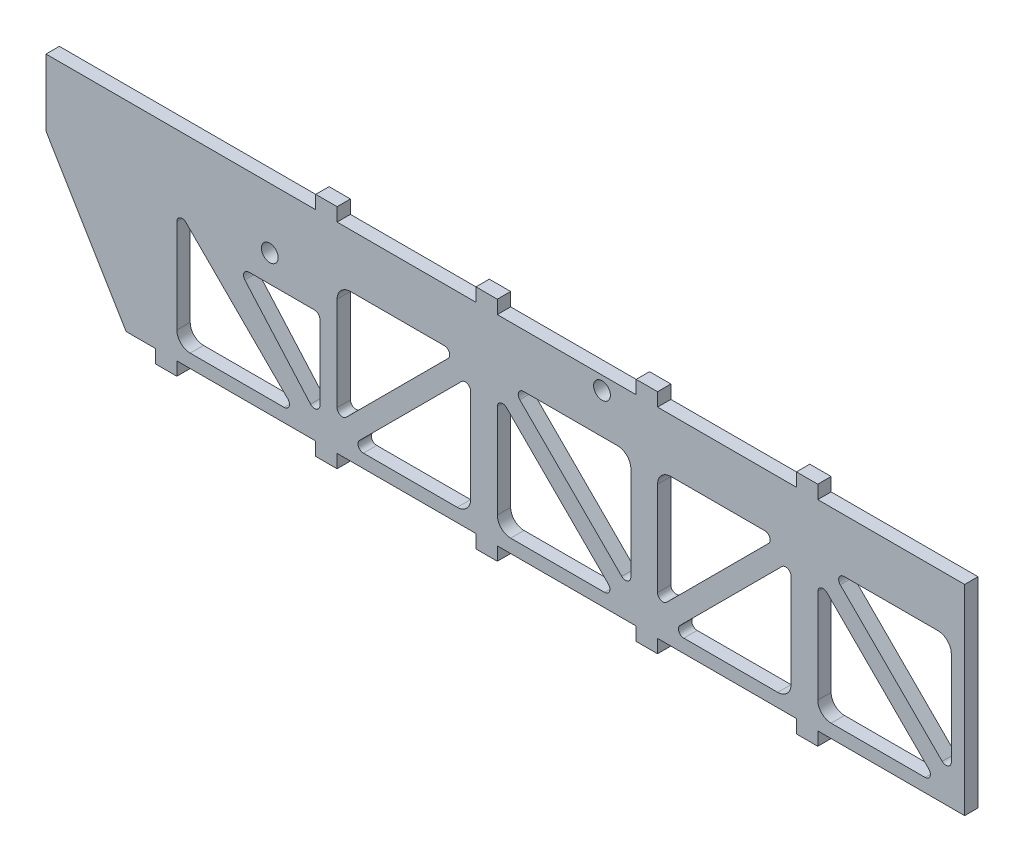
SolidWorks part; units mm, degrees
material "Pine"
ref_plane "Front Plane" through (0, 0, 0) normal (0, 0, 1) x (1, 0, 0)
ref_plane "Top Plane" through (0, 0, 0) normal (0, 1, 0) x (1, 0, 0)
ref_plane "Right Plane" through (0, 0, 0) normal (1, 0, 0) x (0, 0, -1)
sketch "Model" plane through (0, 0, 0) normal (0, 0, 1) x (1, 0, 0)
  line L0 (-306.6281, 15.625) -> (-306.6281, 51.1493)
  line L1 (-309.1681, 53.6893) -> (-340.406, 53.6893)
  line L2 (-342.3135, 49.472) -> (-311.0755, 13.9477)
  line L8 (-171.2321, 6.35) -> (-215.9, 6.35)
  line L9 (-222.25, 57.3679) -> (-222.25, 12.7)
  line L10 (-217.9139, 59.1639) -> (-169.4361, 10.6861)
  line L11 (-234.95, 57.3679) -> (-234.95, 12.7)
  line L12 (-241.3, 6.35) -> (-285.9679, 6.35)
  line L13 (-239.2861, 59.1639) -> (-287.7639, 10.6861)
  line L14 (-294.1139, 17.0361) -> (-245.6361, 65.5139)
  line L15 (-298.45, 63.5) -> (-298.45, 18.8321)
  line L16 (-247.4321, 69.85) -> (-292.1, 69.85)
  line L17 (-323.6321, 6.35) -> (-368.3, 6.35)
  line L18 (-374.65, 57.3679) -> (-374.65, 12.7)
  line L19 (-370.3139, 59.1639) -> (-321.8361, 10.6861)
  line L20 (-18.8321, 6.35) -> (-63.5, 6.35)
  line L21 (-69.85, 57.3679) -> (-69.85, 12.7)
  line L22 (-17.0361, 10.6861) -> (-65.5139, 59.1639)
  line L23 (-82.55, 57.3679) -> (-82.55, 12.7)
  line L24 (-88.9, 6.35) -> (-133.5679, 6.35)
  line L25 (-86.8861, 59.1639) -> (-135.3639, 10.6861)
  line L26 (-93.2361, 65.5139) -> (-141.7139, 17.0361)
  line L27 (-146.05, 63.5) -> (-146.05, 18.8321)
  line L28 (-95.0321, 69.85) -> (-139.7, 69.85)
  line L29 (-163.0861, 17.0361) -> (-211.5639, 65.5139)
  line L30 (-165.1, 69.85) -> (-209.7679, 69.85)
  line L31 (-158.75, 63.5) -> (-158.75, 18.8321)
  line L35 (-398.78, 0) -> (-436.88, 63.5)
  line L36 (0, 0) -> (-398.78, 0)
  line L37 (0, 0) -> (0, 95.25)
  line L38 (0, 95.25) -> (-436.88, 95.25)
  line L39 (-436.88, 63.5) -> (-436.88, 95.25)
  line L40 (-6.35, 63.5) -> (-6.35, 18.8321)
  line L41 (-59.1639, 65.5139) -> (-10.6861, 17.0361)
  line L42 (-12.7, 69.85) -> (-57.3679, 69.85)
  arc A0 (-222.25, 12.7) -> (-215.9, 6.35) centre (-215.9, 12.7) ccw
  arc A1 (-217.9139, 59.1639) -> (-222.25, 57.3679) centre (-219.71, 57.3679) ccw
  arc A2 (-171.2321, 6.35) -> (-169.4361, 10.6861) centre (-171.2321, 8.89) ccw
  arc A3 (-234.95, 57.3679) -> (-239.2861, 59.1639) centre (-237.49, 57.3679) ccw
  arc A4 (-241.3, 6.35) -> (-234.95, 12.7) centre (-241.3, 12.7) ccw
  arc A5 (-287.7639, 10.6861) -> (-285.9679, 6.35) centre (-285.9679, 8.89) ccw
  arc A6 (-245.6361, 65.5139) -> (-247.4321, 69.85) centre (-247.4321, 67.31) ccw
  arc A7 (-298.45, 18.8321) -> (-294.1139, 17.0361) centre (-295.91, 18.8321) ccw
  arc A8 (-292.1, 69.85) -> (-298.45, 63.5) centre (-292.1, 63.5) ccw
  arc A9 (-323.6321, 6.35) -> (-321.8361, 10.6861) centre (-323.6321, 8.89) ccw
  arc A10 (-374.65, 12.7) -> (-368.3, 6.35) centre (-368.3, 12.7) ccw
  arc A11 (-370.3139, 59.1639) -> (-374.65, 57.3679) centre (-372.11, 57.3679) ccw
  arc A12 (-69.85, 12.7) -> (-63.5, 6.35) centre (-63.5, 12.7) ccw
  arc A13 (-65.5139, 59.1639) -> (-69.85, 57.3679) centre (-67.31, 57.3679) ccw
  arc A14 (-18.8321, 6.35) -> (-17.0361, 10.6861) centre (-18.8321, 8.89) ccw
  arc A15 (-82.55, 57.3679) -> (-86.8861, 59.1639) centre (-85.09, 57.3679) ccw
  arc A16 (-88.9, 6.35) -> (-82.55, 12.7) centre (-88.9, 12.7) ccw
  arc A17 (-135.3639, 10.6861) -> (-133.5679, 6.35) centre (-133.5679, 8.89) ccw
  arc A18 (-93.2361, 65.5139) -> (-95.0321, 69.85) centre (-95.0321, 67.31) ccw
  arc A19 (-146.05, 18.8321) -> (-141.7139, 17.0361) centre (-143.51, 18.8321) ccw
  arc A20 (-139.7, 69.85) -> (-146.05, 63.5) centre (-139.7, 63.5) ccw
  arc A21 (-163.0861, 17.0361) -> (-158.75, 18.8321) centre (-161.29, 18.8321) ccw
  arc A22 (-209.7679, 69.85) -> (-211.5639, 65.5139) centre (-209.7679, 67.31) ccw
  arc A23 (-158.75, 63.5) -> (-165.1, 69.85) centre (-165.1, 63.5) ccw
  arc A24 (-306.6281, 15.625) -> (-311.0755, 13.9477) centre (-309.1681, 15.625) cw
  arc A25 (-340.406, 53.6893) -> (-342.3135, 49.472) centre (-340.406, 51.1493) ccw
  arc A26 (-306.6281, 51.1493) -> (-309.1681, 53.6893) centre (-309.1681, 51.1493) ccw
  arc A27 (-10.6861, 17.0361) -> (-6.35, 18.8321) centre (-8.89, 18.8321) ccw
  arc A28 (-57.3679, 69.85) -> (-59.1639, 65.5139) centre (-57.3679, 67.31) ccw
  arc A29 (-6.35, 63.5) -> (-12.7, 69.85) centre (-12.7, 63.5) ccw
  circle A30 centre (-172.466, 88.9) radius 4
  circle A31 centre (-330.454, 66.548) radius 4
  dimension "D2" = 172.466
  dimension "D4" = 8
  dimension "D5" = 157.988
  dimension "D7" = 8
  dimension "D6" = 22.352
  dimension "D8" = 2.54
  dimension "D1" = 95.25
  dimension "D3" = 6.35
extrude "Boss-Extrude1" add sketch "Model" along normal blind 6.35
sketch "Sketch1" plane through (0, 0, 6.35) normal (0, 0, 1) x (1, 0, 0)
  line L0 (-69.85, 95.25) -> (-69.85, 0) construction
  line L1 (-69.85, 57.3679) -> (-69.85, 12.7) construction
  line L2 (-398.78, 0) -> (0, 0) construction
  line L3 (-146.05, 95.25) -> (-146.05, 0) construction
  line L4 (-146.05, 63.5) -> (-146.05, 18.8321) construction
  line L5 (-222.25, 95.25) -> (-222.25, 0) construction
  line L6 (-222.25, 57.3679) -> (-222.25, 12.7) construction
  line L7 (-298.45, 95.25) -> (-298.45, 0) construction
  line L8 (-298.45, 63.5) -> (-298.45, 18.8321) construction
  line L9 (-374.65, 95.25) -> (-374.65, 0) construction
  line L10 (-374.65, 57.3679) -> (-374.65, 12.7) construction
  line L11 (0, 95.25) -> (-436.88, 95.25) construction
  line L12 (-69.85, 0) -> (-80.01, 0)
  line L13 (-69.85, 0) -> (-69.85, -6.35)
  line L14 (-69.85, -6.35) -> (-80.01, -6.35)
  line L15 (-80.01, 0) -> (-80.01, -6.35)
  line L16 (-146.05, 0) -> (-156.21, 0)
  line L17 (-146.05, 0) -> (-146.05, -6.35)
  line L18 (-146.05, -6.35) -> (-156.21, -6.35)
  line L19 (-156.21, 0) -> (-156.21, -6.35)
  line L20 (-222.25, 0) -> (-232.41, 0)
  line L21 (-222.25, 0) -> (-222.25, -6.35)
  line L22 (-222.25, -6.35) -> (-232.41, -6.35)
  line L23 (-232.41, 0) -> (-232.41, -6.35)
  line L24 (-298.45, 0) -> (-308.61, 0)
  line L25 (-298.45, 0) -> (-298.45, -6.35)
  line L26 (-298.45, -6.35) -> (-308.61, -6.35)
  line L27 (-308.61, 0) -> (-308.61, -6.35)
  line L28 (-374.65, 0) -> (-384.81, 0)
  line L29 (-374.65, 0) -> (-374.65, -6.35)
  line L30 (-374.65, -6.35) -> (-384.81, -6.35)
  line L31 (-384.81, 0) -> (-384.81, -6.35)
  line L37 (-298.45, 95.25) -> (-308.61, 95.25)
  line L38 (-298.45, 95.25) -> (-298.45, 101.6)
  line L39 (-298.45, 101.6) -> (-308.61, 101.6)
  line L40 (-308.61, 95.25) -> (-308.61, 101.6)
  line L41 (-222.25, 95.25) -> (-232.41, 95.25)
  line L42 (-222.25, 95.25) -> (-222.25, 101.6)
  line L43 (-222.25, 101.6) -> (-232.41, 101.6)
  line L44 (-232.41, 95.25) -> (-232.41, 101.6)
  line L45 (-146.05, 95.25) -> (-156.21, 95.25)
  line L46 (-146.05, 95.25) -> (-146.05, 101.6)
  line L47 (-146.05, 101.6) -> (-156.21, 101.6)
  line L48 (-156.21, 95.25) -> (-156.21, 101.6)
  line L49 (-69.85, 95.25) -> (-80.01, 95.25)
  line L50 (-69.85, 95.25) -> (-69.85, 101.6)
  line L51 (-69.85, 101.6) -> (-80.01, 101.6)
  line L52 (-80.01, 95.25) -> (-80.01, 101.6)
  dimension "D1" = 6.35
  dimension "D2" = 10.16
  dimension "D3" = 10.16
  dimension "D4" = 10.16
  dimension "D5" = 10.16
  dimension "D6" = 10.16
  dimension "D7" = 6.35
  dimension "D9" = 10.16
  dimension "D10" = 10.16
  dimension "D11" = 10.16
  dimension "D12" = 10.16
extrude "Boss-Extrude2" add sketch "Sketch1" against normal up to surface (6.35 mm away) up to face at (-168.466, 88.9, 0)
equation "\"thick\"=0.25"
equation "\"D1@Boss-Extrude1\"=\"thick\""
